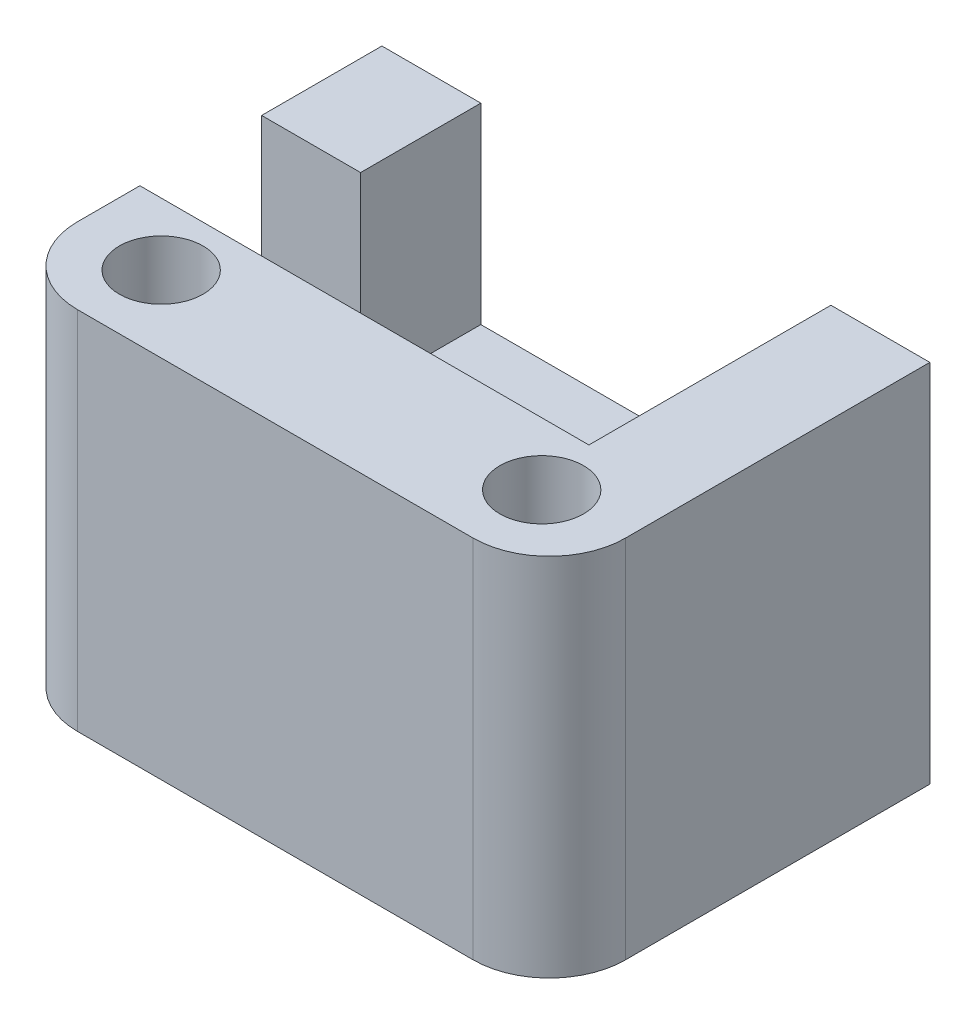
SolidWorks part; units mm, degrees
material "ABS"
ref_plane "Front Plane" through (0, 0, 0) normal (0, 0, 1) x (1, 0, 0)
ref_plane "Top Plane" through (0, 0, 0) normal (0, 1, 0) x (1, 0, 0)
ref_plane "Right Plane" through (0, 0, 0) normal (1, 0, 0) x (0, 0, -1)
sketch "Sketch2" plane through (0, 0, 0) normal (0, 1, 0) x (1, 0, 0)
  line L1 (0, 0) -> (36, 0)
  line L2 (0, 0) -> (0, 25)
  line L3 (0, 25) -> (36, 25)
  line L4 (36, 0) -> (36, 25)
  dimension "D1" = 36
  dimension "D2" = 25
extrude "Boss-Extrude1" add sketch "Sketch2" along normal blind 24
sketch "Sketch3" plane through (0, 24, 0) normal (0, 1, 0) x (1, 0, 0)
  line L0 (36, 25) -> (0, 25) construction
  line L1 (6.5, 25) -> (29.5, 25)
  line L2 (6.5, 25) -> (6.5, 14.1)
  line L3 (6.5, 9.1) -> (29.5, 9.1)
  line L4 (29.5, 25) -> (29.5, 9.1)
  line L6 (6.5, 9.1) -> (5.5, 9.1)
  line L7 (0, 25) -> (0, 0) construction
  line L9 (6.5, 14.1) -> (5.5, 14.1)
  line L10 (5.5, 9.1) -> (5.5, 14.1)
  dimension "D1" = 23
  dimension "D2" = 6.5
  dimension "D3" = 15.9
  dimension "D4" = 1
  dimension "D5" = 5
  dimension "D6" = 1
extrude "Cut-Extrude1" cut sketch "Sketch3" against normal blind 12.6
hole_wizard "Tap Drill for M2.5x0.45 Tap1" positions "Sketch4" profile "Sketch5" hole size "M2.5x0.45" standard "ANSI Metric"
sketch "Sketch4" plane through (0, 0, -25) normal (0, 0, -1) x (-1, 0, 0)
  line L0 (-29.5, 11.4) -> (-29.5, 24) construction
  line L1 (-36, 24) -> (-29.5, 24) construction
  line L2 (-6.5, 11.4) -> (-6.5, 24) construction
  line L3 (-6.5, 24) -> (0, 24) construction
  point P0 (-32.5, 17.7)
  point P2 (-3.5, 17.7)
  point P7 (-29.5, 17.7)
  point P10 (-32.75, 24)
  dimension "D1" = 3
  dimension "D2" = 6.3
  dimension "D3" = 3
  dimension "D4" = 6.3
sketch "Sketch5" plane through (32.5, 17.7, -25) normal (1, 0, 0) x (0, 1, 0)
  line L0 (0, 0) -> (0, 6)
  line L1 (0, 6) -> (1.025, 6)
  line L2 (1.025, 6) -> (1.025, 0)
  line L5 (1.025, 0) -> (0, 0)
  line L10 (0, 6) -> (-1.025, 6) construction
  line L11 (0, -6.35) -> (0, 107.95) construction
  dimension "Hole Dia." = 2.05
  dimension "Hole Depth" = 6
  dimension "Drill Angle" = 180
fillet "Fillet2" radius 5 1 edges at (36, 12, 0)
hole_wizard "CBORE for M2.5 SHCS1" positions "Sketch6" profile "Sketch7" counterbore size "M2.5" standard "ANSI Metric" end condition through all
sketch "Sketch6" plane through (0, 24, 0) normal (0, 1, 0) x (1, 0, 0)
  line L3 (36, 25) -> (29.5, 25) construction
  line L5 (6.5, 25) -> (0, 25) construction
  line L6 (0, 25) -> (0, 0) construction
  point P0 (30.5, 5)
  point P2 (5.5, 5)
  point P19 (32.75, 25)
  dimension "D1" = 25
  dimension "D2" = 5.5
  dimension "D3" = 20
  dimension "D5" = 20
sketch "Sketch7" plane through (30.5, 24, -5) normal (1, 0, 0) x (0, 0, 1)
  line L0 (0, 0) -> (0, 24)
  line L1 (0, 24) -> (1.5, 24)
  line L3 (1.5, 24) -> (1.5, 4)
  line L4 (1.5, 4) -> (2.75, 4)
  line L5 (2.75, 4) -> (2.75, 0)
  line L7 (2.75, 0) -> (0, 0)
  line L11 (0, -6.35) -> (0, 107.95) construction
  dimension "Thru Hole Dia." = 3
  dimension "Thru Hole Depth" = 24
  dimension "C'Bore Dia." = 5.5
  dimension "C'Bore Depth" = 4
sketch "Sketch8" plane through (0, 0, 0) normal (-1, 0, 0) x (0, 0, 1)
  line L0 (-9.1, 11.4) -> (-9.1, 24) construction
  line L1 (-9.1, 24) -> (-17.1, 24)
  line L2 (-9.1, 24) -> (-9.1, 14)
  line L3 (-9.1, 14) -> (-17.1, 14)
  line L4 (-17.1, 24) -> (-17.1, 14)
  line L5 (-25, 24) -> (0, 24) construction
  point P8 (-12.5, 24)
  dimension "D1" = 10
  dimension "D2" = 0
  dimension "D3" = 8
extrude "Cut-Extrude2" cut sketch "Sketch8" against normal blind 10
fillet "Fillet3" radius 5 1 edges at (0, 12, 0)
